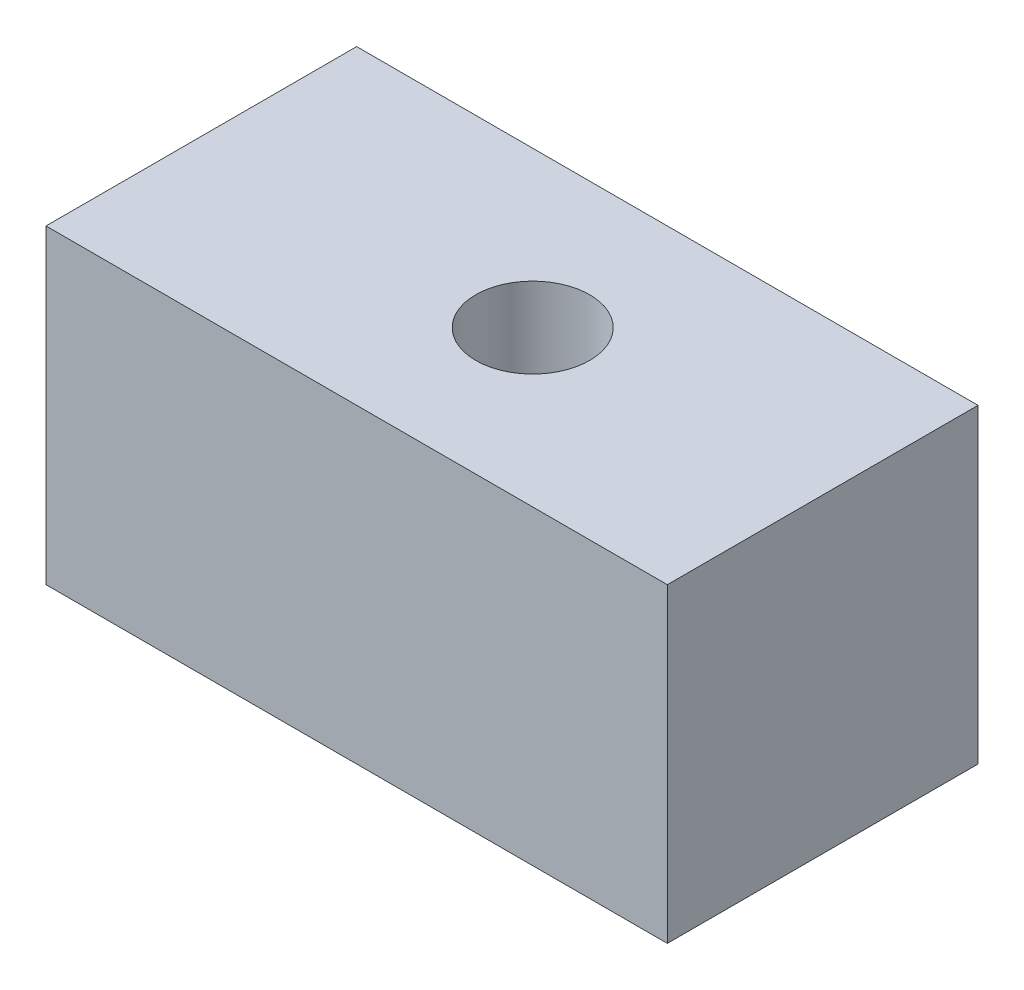
SolidWorks part; units mm, degrees
ref_plane "Front Plane" through (0, 0, 0) normal (0, 0, 1) x (1, 0, 0)
ref_plane "Top Plane" through (0, 0, 0) normal (0, 1, 0) x (1, 0, 0)
ref_plane "Right Plane" through (0, 0, 0) normal (1, 0, 0) x (0, 0, -1)
sketch "Sketch1" plane through (0, 0, 0) normal (1, 0, 0) x (0, 0, -1)
  line L1 (-7.5, 7.5) -> (7.5, 7.5)
  line L2 (-7.5, 7.5) -> (-7.5, -7.5)
  line L3 (-7.5, -7.5) -> (7.5, -7.5)
  line L4 (7.5, 7.5) -> (7.5, -7.5)
  line L5 (-7.5, 7.5) -> (7.5, -7.5) construction
  line L6 (-7.5, -7.5) -> (7.5, 7.5) construction
  point P0 (0, 0)
  dimension "D1" = 15
  dimension "D2" = 15
extrude "Boss-Extrude1" add sketch "Sketch1" along normal blind 30
sketch "Sketch2" plane through (0, 7.5, 0) normal (0, 1, 0) x (1, 0, 0)
  line L0 (0, 7.5) -> (0, -7.5) construction
  circle A0 centre (16, 0) radius 2.75
  dimension "D1" = 5.5
  dimension "D2" = 16
extrude "Cut-Extrude1" cut sketch "Sketch2" against normal through all
sketch "Sketch3" plane through (0, 0, -7.5) normal (0, 0, -1) x (-1, 0, 0)
  line L0 (0, -7.5) -> (0, 7.5) construction
  line L1 (0, 3.5) -> (-10, 3.5)
  line L2 (0, 3.5) -> (0, -3.358)
  line L3 (0, -3.358) -> (-10, -3.358)
  line L4 (-10, 3.5) -> (-10, -3.358)
  line L5 (-10, 0.071) -> (-4.92, 0.071) construction
  line L6 (-30, 7.5) -> (0, 7.5) construction
  circle A0 centre (-4.92, 0.071) radius 1.5875
  dimension "D2" = 3.175
  dimension "D1" = 6.858
  dimension "D3" = 5.08
  dimension "D4" = 10
  dimension "D5" = 4
extrude "Cut-Extrude2" cut sketch "Sketch3" against normal blind 1
sketch "Sketch5" plane through (0, 0, -7.5) normal (0, 0, -1) x (-1, 0, 0)
  line L0 (0, -7.5) -> (0, -3.358)
  line L1 (0, -7.5) -> (-3.9016, -7.5)
  line L2 (-30, -7.5) -> (0, -7.5) construction
